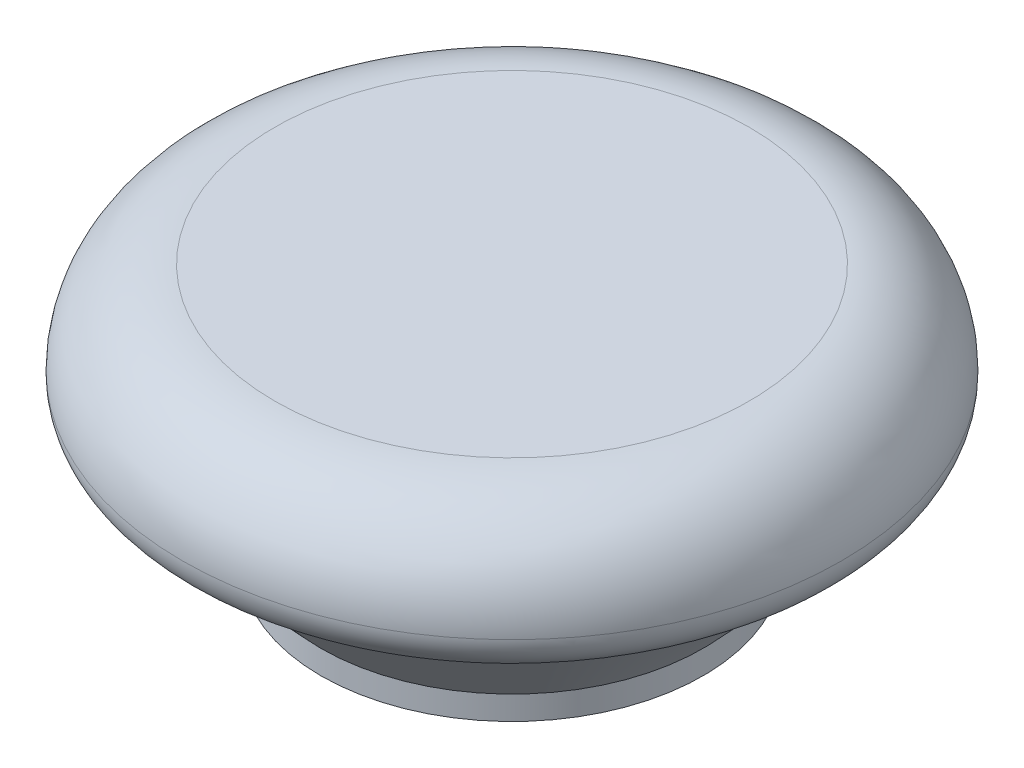
SolidWorks part; units mm, degrees
ref_plane "Front Plane" through (0, 0, 0) normal (0, 0, 1) x (1, 0, 0)
ref_plane "Top Plane" through (0, 0, 0) normal (0, 1, 0) x (1, 0, 0)
ref_plane "Right Plane" through (0, 0, 0) normal (1, 0, 0) x (0, 0, -1)
sketch "Sketch1" plane through (0, 0, 0) normal (0, 1, 0) x (1, 0, 0)
  circle A0 centre (0, 0) radius 3
  dimension "D1" = 6
ref_plane "Plane1" through (0, 8, 0) normal (0, 1, 0) x (1, 0, 0)
sketch "Sketch2" plane through (0, 8, 0) normal (0, 1, 0) x (1, 0, 0)
  circle A0 centre (0, 0) radius 7
  dimension "D1" = 14
loft "Loft1" add profiles "Sketch1", "Sketch2" connector at (-1.2259, 0, 2.7381) connector at (-2.8083, 8, 6.412)
sketch "Sketch3" plane through (0, 0, 0) normal (0, -1, 0) x (1, 0, 0)
  circle A0 centre (0, 0) radius 2
  dimension "D1" = 4
extrude "Cut-Extrude1" cut sketch "Sketch3" against normal up to surface (8 mm away) up to face at (0, 8, 7)
fillet "Fillet1" radius 0.45 1 edges at (0, 0, 3)
fillet "Fillet2" radius 0.4 1 edges at (0, 0, -2)
sketch "Sketch4" plane through (0, 8, 0) normal (0, 1, 0) x (1, 0, 0)
  circle A0 centre (0, 0) radius 14.5
  dimension "D1" = 29
extrude "Boss-Extrude1" add sketch "Sketch4" along normal blind 1.8
ref_plane "Plane2" through (0, 17.8, 0) normal (0, 1, 0) x (1, 0, 0)
sketch "Sketch5" plane through (0, 17.8, 0) normal (0, 1, 0) x (1, 0, 0)
  circle A0 centre (0, 0) radius 25
  dimension "D1" = 50
extrude "Boss-Extrude2" add sketch "Sketch5" along normal blind 3 separate body
fillet "Fillet3" radius 3 1 edges at (0, 17.8, 25)
sketch "Sketch6" plane through (0, 17.8, 0) normal (0, -1, 0) x (1, 0, 0)
  circle A0 centre (0, 0) radius 22
sketch "Sketch7" plane through (0, 9.8, 0) normal (0, 1, 0) x (1, 0, 0)
  circle A0 centre (0, 0) radius 14.5
  dimension "D1" = 29
loft "Loft3" add profiles "Sketch7", "Sketch6" connector at (-14.1327, 9.8, -3.243) connector at (-20.7408, 17.8, -7.3362)
sketch "Sketch8" plane through (0, 20.8, 0) normal (0, 1, 0) x (1, 0, 0)
  circle A0 centre (0, 0) radius 25
extrude "Boss-Extrude3" add sketch "Sketch8" along normal blind 7
fillet "Fillet4" radius 7 1 edges at (0, 27.8, 25)
sketch "Sketch9" plane through (0, 27.8, 0) normal (0, 1, 0) x (1, 0, 0)
  line L0 (-8.8184, -27.3925) -> (15.6016, -27.3925) construction
